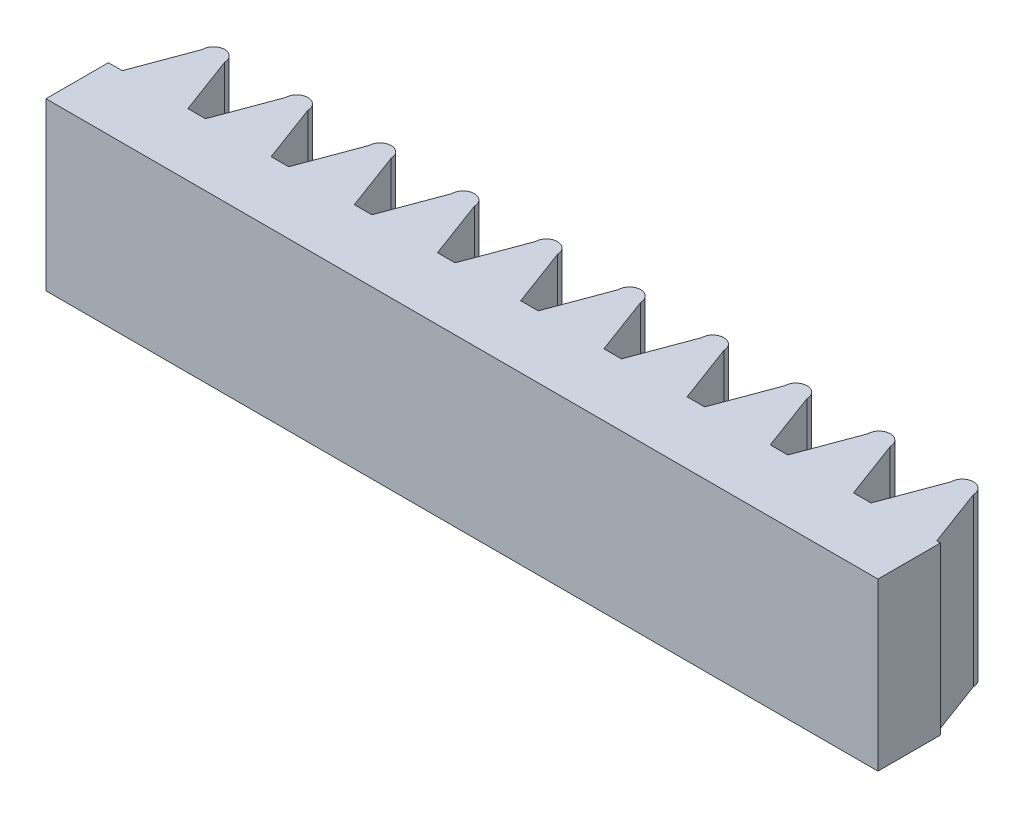
SolidWorks part; units mm, degrees
ref_plane "Front Plane" through (0, 0, 0) normal (0, 0, 1) x (1, 0, 0)
ref_plane "Top Plane" through (0, 0, 0) normal (0, 1, 0) x (1, 0, 0)
ref_plane "Right Plane" through (0, 0, 0) normal (1, 0, 0) x (0, 0, -1)
sketch "Base" plane through (0, 0, 0) normal (0, 1, 0) x (1, 0, 0)
  line L1 (0, 0) -> (20, 0)
  line L2 (0, 0) -> (0, -1.5)
  line L3 (0, -1.5) -> (20, -1.5)
  line L4 (20, 0) -> (20, -1.5)
  dimension "D1" = 20
  dimension "D2" = 1.5
sketch "Gears-1" plane through (0, 0, 0) normal (0, 1, 0) x (1, 0, 0)
  line L0 (0.3327, 0) -> (0.8553, 1.406)
  line L1 (0, 0) -> (20, 0) construction
  line L2 (1.1222, 1.673) -> (1.1222, 2.653) construction
  line L3 (1.9117, 0) -> (1.3892, 1.406)
  line L4 (0.3327, 0) -> (1.9117, 0)
  line L5 (2.3327, 0) -> (3.9117, 0)
  line L6 (3.9117, 0) -> (3.3892, 1.406)
  line L7 (2.3327, 0) -> (2.8553, 1.406)
  line L8 (4.3327, 0) -> (5.9117, 0)
  line L9 (5.9117, 0) -> (5.3892, 1.406)
  line L10 (4.3327, 0) -> (4.8553, 1.406)
  line L11 (6.3327, 0) -> (7.9117, 0)
  line L12 (7.9117, 0) -> (7.3892, 1.406)
  line L13 (6.3327, 0) -> (6.8553, 1.406)
  line L14 (8.3327, 0) -> (9.9117, 0)
  line L15 (9.9117, 0) -> (9.3892, 1.406)
  line L16 (8.3327, 0) -> (8.8553, 1.406)
  line L17 (10.3327, 0) -> (11.9117, 0)
  line L18 (11.9117, 0) -> (11.3892, 1.406)
  line L19 (10.3327, 0) -> (10.8553, 1.406)
  line L20 (12.3327, 0) -> (13.9117, 0)
  line L21 (13.9117, 0) -> (13.3892, 1.406)
  line L22 (12.3327, 0) -> (12.8553, 1.406)
  line L23 (14.3327, 0) -> (15.9117, 0)
  line L24 (15.9117, 0) -> (15.3892, 1.406)
  line L25 (14.3327, 0) -> (14.8553, 1.406)
  line L26 (16.3327, 0) -> (17.9117, 0)
  line L27 (17.9117, 0) -> (17.3892, 1.406)
  line L28 (16.3327, 0) -> (16.8553, 1.406)
  line L29 (18.3327, 0) -> (19.9117, 0)
  line L30 (19.9117, 0) -> (19.3892, 1.406)
  line L31 (18.3327, 0) -> (18.8553, 1.406)
  arc A0 (0.8553, 1.406) -> (1.3892, 1.406) centre (1.1222, 1.406) cw
  arc A1 (2.8553, 1.406) -> (3.3892, 1.406) centre (3.1222, 1.406) cw
  arc A2 (4.8553, 1.406) -> (5.3892, 1.406) centre (5.1222, 1.406) cw
  arc A3 (6.8553, 1.406) -> (7.3892, 1.406) centre (7.1222, 1.406) cw
  arc A4 (8.8553, 1.406) -> (9.3892, 1.406) centre (9.1222, 1.406) cw
  arc A5 (10.8553, 1.406) -> (11.3892, 1.406) centre (11.1222, 1.406) cw
  arc A6 (12.8553, 1.406) -> (13.3892, 1.406) centre (13.1222, 1.406) cw
  arc A7 (14.8553, 1.406) -> (15.3892, 1.406) centre (15.1222, 1.406) cw
  arc A8 (16.8553, 1.406) -> (17.3892, 1.406) centre (17.1222, 1.406) cw
  arc A9 (18.8553, 1.406) -> (19.3892, 1.406) centre (19.1222, 1.406) cw
  dimension "D1" = 10
extrude "Boss-Extrude1" add sketch "Gears-1" along normal blind 4
extrude "Boss-Extrude2" add sketch "Base" along normal blind 4
